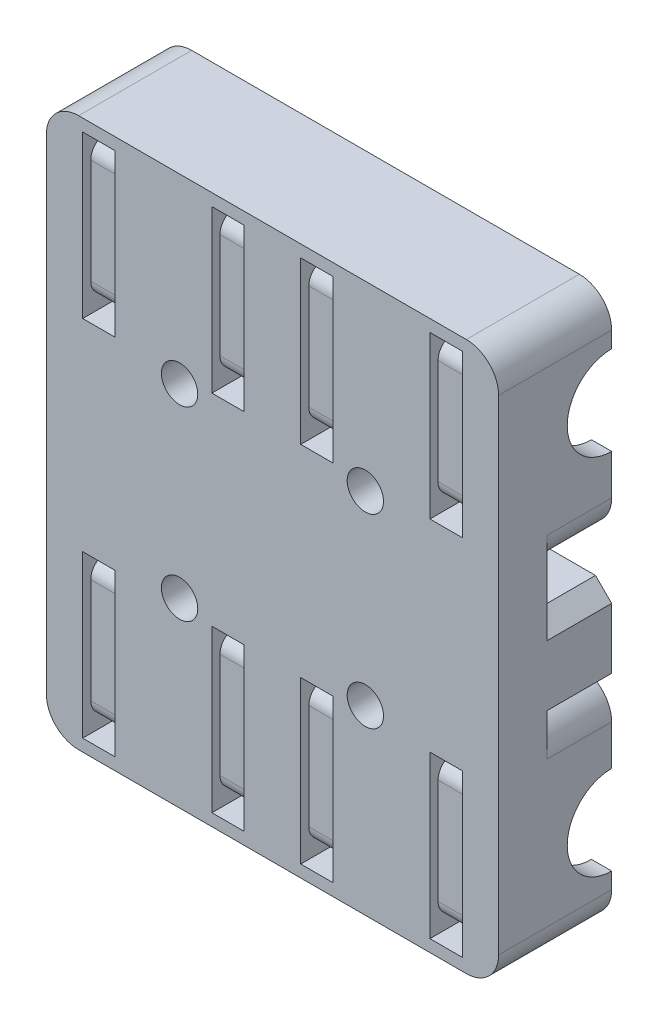
SolidWorks part; units mm, degrees
material "ABS"
ref_plane "Front Plane" through (0, 0, 0) normal (0, 0, 1) x (1, 0, 0)
ref_plane "Top Plane" through (0, 0, 0) normal (0, 1, 0) x (1, 0, 0)
ref_plane "Right Plane" through (0, 0, 0) normal (1, 0, 0) x (0, 0, -1)
sketch "Sketch1" plane through (0, 0, 0) normal (0, 0, 1) x (1, 0, 0)
  line L1 (0, 0) -> (56, 0)
  line L2 (0, 0) -> (0, 68)
  line L3 (0, 68) -> (56, 68)
  line L4 (56, 0) -> (56, 68)
  dimension "D1" = 68
  dimension "D2" = 56
extrude "Boss-Extrude1" add sketch "Sketch1" along normal blind 14
sketch "Sketch2" plane through (0, 0, 14) normal (0, 0, 1) x (1, 0, 0)
  line L0 (0, 34) -> (56, 34) construction
  line L1 (4, 68) -> (52, 68)
  line L2 (0, 64) -> (0, 4)
  line L3 (4, 0) -> (52, 0)
  line L4 (56, 64) -> (56, 4)
  line L5 (4.5, 47.25) -> (0, 47.25) construction
  line L6 (4.5, 48) -> (8.5, 48)
  line L7 (39.5, 45.5) -> (16.5, 45.5) construction
  line L8 (28, 45.5) -> (28, 68) construction
  line L9 (4.5, 48) -> (4.5, 46.5)
  line L10 (4.5, 46.5) -> (8.5, 46.5)
  line L11 (8.5, 48) -> (8.5, 46.5)
  line L12 (0, 68) -> (0, 0) construction
  line L13 (8.5, 47.25) -> (20.5, 47.25) construction
  line L14 (24.5, 47.25) -> (31.5, 47.25) construction
  line L15 (20.5, 48) -> (24.5, 48)
  line L16 (20.5, 48) -> (20.5, 46.5)
  line L17 (20.5, 46.5) -> (24.5, 46.5)
  line L18 (24.5, 48) -> (24.5, 46.5)
  line L19 (35.5, 47.25) -> (47.5, 47.25) construction
  line L20 (31.5, 48) -> (35.5, 48)
  line L21 (31.5, 48) -> (31.5, 46.5)
  line L22 (31.5, 46.5) -> (35.5, 46.5)
  line L23 (35.5, 48) -> (35.5, 46.5)
  line L24 (51.5, 47.25) -> (56, 47.25) construction
  line L25 (47.5, 48) -> (51.5, 48)
  line L26 (47.5, 48) -> (47.5, 46.5)
  line L27 (47.5, 46.5) -> (51.5, 46.5)
  line L28 (51.5, 48) -> (51.5, 46.5)
  line L29 (0, 56.5) -> (56, 56.5) construction
  line L30 (47.5, 65) -> (51.5, 65)
  line L31 (51.5, 65) -> (51.5, 66.5)
  line L32 (47.5, 66.5) -> (51.5, 66.5)
  line L33 (47.5, 65) -> (47.5, 66.5)
  line L34 (35.5, 65) -> (35.5, 66.5)
  line L35 (31.5, 65) -> (35.5, 65)
  line L36 (31.5, 66.5) -> (35.5, 66.5)
  line L37 (31.5, 65) -> (31.5, 66.5)
  line L38 (20.5, 65) -> (24.5, 65)
  line L39 (20.5, 65) -> (20.5, 66.5)
  line L40 (24.5, 65) -> (24.5, 66.5)
  line L41 (20.5, 66.5) -> (24.5, 66.5)
  line L42 (8.5, 65) -> (8.5, 66.5)
  line L43 (4.5, 65) -> (8.5, 65)
  line L44 (4.5, 66.5) -> (8.5, 66.5)
  line L45 (4.5, 65) -> (4.5, 66.5)
  line L46 (8.5, 20) -> (8.5, 21.5)
  line L47 (4.5, 21.5) -> (8.5, 21.5)
  line L48 (4.5, 20) -> (4.5, 21.5)
  line L49 (4.5, 20) -> (8.5, 20)
  line L50 (24.5, 20) -> (24.5, 21.5)
  line L51 (20.5, 21.5) -> (24.5, 21.5)
  line L52 (20.5, 20) -> (20.5, 21.5)
  line L53 (20.5, 20) -> (24.5, 20)
  line L54 (35.5, 20) -> (35.5, 21.5)
  line L55 (31.5, 21.5) -> (35.5, 21.5)
  line L56 (31.5, 20) -> (31.5, 21.5)
  line L57 (31.5, 20) -> (35.5, 20)
  line L58 (51.5, 20) -> (51.5, 21.5)
  line L59 (47.5, 21.5) -> (51.5, 21.5)
  line L60 (47.5, 20) -> (47.5, 21.5)
  line L61 (47.5, 20) -> (51.5, 20)
  line L62 (47.5, 3) -> (47.5, 1.5)
  line L63 (47.5, 1.5) -> (51.5, 1.5)
  line L64 (51.5, 3) -> (51.5, 1.5)
  line L65 (47.5, 3) -> (51.5, 3)
  line L66 (31.5, 3) -> (31.5, 1.5)
  line L67 (31.5, 1.5) -> (35.5, 1.5)
  line L68 (31.5, 3) -> (35.5, 3)
  line L69 (35.5, 3) -> (35.5, 1.5)
  line L70 (20.5, 1.5) -> (24.5, 1.5)
  line L71 (24.5, 3) -> (24.5, 1.5)
  line L72 (20.5, 3) -> (20.5, 1.5)
  line L73 (20.5, 3) -> (24.5, 3)
  line L74 (4.5, 3) -> (4.5, 1.5)
  line L75 (4.5, 1.5) -> (8.5, 1.5)
  line L76 (4.5, 3) -> (8.5, 3)
  line L77 (8.5, 3) -> (8.5, 1.5)
  arc A0 (56, 4) -> (52, 0) centre (52, 4) cw
  arc A1 (4, 0) -> (0, 4) centre (4, 4) cw
  arc A2 (56, 64) -> (52, 68) centre (52, 64) ccw
  arc A3 (4, 68) -> (0, 64) centre (4, 64) ccw
  circle A4 centre (16.5, 22.5) radius 2.25
  circle A5 centre (16.5, 45.5) radius 2.25
  circle A6 centre (39.5, 45.5) radius 2.25
  circle A7 centre (39.5, 22.5) radius 2.25
  point P8 (56, 0)
  point P15 (0, 68)
  line M29 (0, 68) -> (0, 0)
  line M30 (0, 0) -> (56, 0)
  line M31 (56, 0) -> (56, 68)
  line M32 (56, 68) -> (0, 68)
  dimension "D1" = 4
  dimension "D2" = 4.5
  dimension "D3" = 23
  dimension "D4" = 22.5
  dimension "D5" = 1.5
  dimension "D6" = 4
  dimension "D7" = 4.5
  dimension "D8" = 12
  dimension "D9" = 20.75
  dimension "D10" = 9.25
extrude "Cut-Extrude1" cut sketch "Sketch2" against normal through all contours L45 L43 L42 L44 | L41 L39 L38 L40 | L37 L35 L34 L36 | L28 L25 L26 L27 | A6 | L23 L20 L21 L22 | L18 L15 L16 L17 | A5 | L11 L6 L9 L10 | L48 L49 L46 L47 | A4 | L52 L53 L50 L51 | A7 | L73 L72 L70 L71 | A1 M30 M29 | A0 M31 M30 | A3 M32 M29 | A2 M31 M32 | L30 L31 L32 L33 | L57 L54 L55 L56 | L59 L58 L61 L60 | L65 L64 L63 L62 | L67 L69 L68 L66 | L75 L77 L76 L74 region at (0.8935, 67.1065, 14) region at (55.1065, 67.1065, 14) region at (0.8935, 0.8935, 14) region at (55.1065, 0.8935, 14) region at (6.5, 47.25, 14) region at (22.5, 47.25, 14) region at (33.5, 47.25, 14) region at (49.5, 47.25, 14) region at (33.5, 65.75, 14) region at (22.5, 65.75, 14) region at (6.5, 65.75, 14) region at (6.5, 20.75, 14) region at (22.5, 20.75, 14) region at (22.5, 2.25, 14) region at (16.5, 22.5, 14) region at (16.5, 45.5, 14) region at (39.5, 45.5, 14) region at (39.5, 22.5, 14)
sketch "Sketch3" plane through (0, 0, 14) normal (0, 0, 1) x (1, 0, 0)
  line L0 (56, 34) -> (0, 34) construction
  line L1 (4.5, 65) -> (8.5, 65)
  line L2 (4.5, 65) -> (4.5, 48)
  line L3 (4.5, 48) -> (8.5, 48)
  line L4 (8.5, 65) -> (8.5, 48)
  line L5 (20.5, 65) -> (24.5, 65)
  line L6 (20.5, 65) -> (20.5, 48)
  line L7 (20.5, 48) -> (24.5, 48)
  line L8 (24.5, 65) -> (24.5, 48)
  line L9 (31.5, 65) -> (35.5, 65)
  line L10 (31.5, 65) -> (31.5, 48)
  line L11 (31.5, 48) -> (35.5, 48)
  line L12 (35.5, 65) -> (35.5, 48)
  line L13 (47.5, 65) -> (51.5, 65)
  line L14 (47.5, 65) -> (47.5, 48)
  line L15 (47.5, 48) -> (51.5, 48)
  line L16 (51.5, 65) -> (51.5, 48)
  line L17 (56, 4) -> (56, 64) construction
  line L18 (0, 64) -> (0, 4) construction
  line L19 (51.5, 3) -> (51.5, 20)
  line L20 (47.5, 20) -> (51.5, 20)
  line L21 (47.5, 3) -> (47.5, 20)
  line L22 (47.5, 3) -> (51.5, 3)
  line L23 (35.5, 3) -> (35.5, 20)
  line L24 (31.5, 20) -> (35.5, 20)
  line L25 (31.5, 3) -> (31.5, 20)
  line L26 (31.5, 3) -> (35.5, 3)
  line L27 (24.5, 3) -> (24.5, 20)
  line L28 (20.5, 20) -> (24.5, 20)
  line L29 (20.5, 3) -> (20.5, 20)
  line L30 (20.5, 3) -> (24.5, 3)
  line L31 (8.5, 3) -> (8.5, 20)
  line L32 (4.5, 20) -> (8.5, 20)
  line L33 (4.5, 3) -> (4.5, 20)
  line L34 (4.5, 3) -> (8.5, 3)
extrude "Cut-Extrude2" cut sketch "Sketch3" against normal blind 1
ref_plane "Plane2" through (53.5, 0, 0) normal (1, 0, 0) x (0, 0, -1)
sketch "Sketch5" plane through (53.5, 0, 0) normal (1, 0, 0) x (0, 0, -1)
  line L0 (0, 4) -> (0, 64) construction
  line L1 (0, 0) -> (-14, 0) construction
  circle A0 centre (0, 11.5) radius 7.5
  dimension "D1" = 15
  dimension "D2" = 11.5
extrude "Cut-Extrude3" cut sketch "Sketch5" against normal blind 24.5 contours A0
ref_plane "Plane3" through (28, 0, 0) normal (1, 0, 0) x (0, 0, -1)
ref_plane "Plane4" through (0, 34, 0) normal (0, -1, 0) x (-1, 0, 0)
mirror "Mirror1" about plane through (28, 0, 0) normal (1, 0, 0) of "Cut-Extrude3"
sketch "Sketch7" plane through (56, 0, 0) normal (1, 0, 0) x (0, 0, -1)
  line L0 (0, 4) -> (0, 64) construction
  line L1 (0, 0) -> (-14, 0) construction
  circle A0 centre (0, 11.5) radius 5.5
  dimension "D1" = 11
  dimension "D2" = 11.5
extrude "Cut-Extrude4" cut sketch "Sketch7" against normal through all
mirror "Mirror3" about plane through (0, 34, 0) normal (0, -1, 0) of "Cut-Extrude3", "Mirror1", "Cut-Extrude4"
fillet "Fillet1" radius 2 16 edges at (49.5, 3, 13) (33.5, 3, 13) (22.5, 3, 13) (6.5, 3, 13) (6.5, 20, 13) (22.5, 20, 13) (33.5, 20, 13) (49.5, 20, 13) (6.5, 48, 13) (6.5, 65, 13) (22.5, 65, 13) (22.5, 48, 13) (33.5, 48, 13) (33.5, 65, 13) (49.5, 65, 13) (49.5, 48, 13)
sketch "Sketch9" plane through (0, 0, 0) normal (0, 0, -1) x (-1, 0, 0)
  line L0 (-54.91, 27.45) -> (-54.01, 27.45) construction
  line L1 (-52.4311, 27.702) -> (-52.2422, 27.3355)
  line L2 (-53.5978, 27.3355) -> (-53.4089, 27.702)
  line L3 (-54.4211, 27.702) -> (-54.2322, 27.3355)
  line L4 (-54.01, 27.2) -> (-53.82, 27.2)
  line L5 (-55.5878, 27.3355) -> (-55.3989, 27.702)
  line L6 (-54.91, 27.45) -> (-55.81, 27.45) construction
  line L7 (-55.81, 27.2) -> (-56, 27.2)
  line L8 (-50.4411, 27.702) -> (-50.2522, 27.3355)
  line L9 (-29, 19) -> (-53.5, 19) construction
  line L10 (-56, 17) -> (-56, 51) construction
  line L12 (-51.6078, 27.3355) -> (-51.4189, 27.702)
  line L13 (-51.83, 27.2) -> (-52.02, 27.2)
  line L14 (-48.4511, 27.702) -> (-48.2622, 27.3355)
  line L15 (-49.6178, 27.3355) -> (-49.4289, 27.702)
  line L16 (-49.84, 27.2) -> (-50.03, 27.2)
  line L17 (-46.4611, 27.702) -> (-46.2722, 27.3355)
  line L18 (-47.6278, 27.3355) -> (-47.4389, 27.702)
  line L19 (-47.85, 27.2) -> (-48.04, 27.2)
  line L20 (-44.4711, 27.702) -> (-44.2822, 27.3355)
  line L21 (-45.6378, 27.3355) -> (-45.4489, 27.702)
  line L22 (-45.86, 27.2) -> (-46.05, 27.2)
  line L23 (-42.4811, 27.702) -> (-42.2922, 27.3355)
  line L24 (-43.6478, 27.3355) -> (-43.4589, 27.702)
  line L25 (-43.87, 27.2) -> (-44.06, 27.2)
  line L26 (-40.4911, 27.702) -> (-40.3022, 27.3355)
  line L27 (-41.6578, 27.3355) -> (-41.4689, 27.702)
  line L28 (-41.88, 27.2) -> (-42.07, 27.2)
  line L29 (-38.5011, 27.702) -> (-38.3122, 27.3355)
  line L30 (-39.6678, 27.3355) -> (-39.4789, 27.702)
  line L31 (-39.89, 27.2) -> (-40.08, 27.2)
  line L32 (-36.5111, 27.702) -> (-36.3222, 27.3355)
  line L33 (-37.6778, 27.3355) -> (-37.4889, 27.702)
  line L34 (-37.9, 27.2) -> (-38.09, 27.2)
  line L35 (-34.5211, 27.702) -> (-34.3322, 27.3355)
  line L36 (-35.6878, 27.3355) -> (-35.4989, 27.702)
  line L37 (-35.91, 27.2) -> (-36.1, 27.2)
  line L38 (-34.11, 27.2) -> (-34.11, 34.7)
  line L39 (-36.11, 36.7) -> (-54, 36.7)
  line L40 (-56, 34.7) -> (-56, 27.2)
  line L41 (-54, 36.7) -> (-56, 34.7)
  line L42 (-34.11, 34.7) -> (-36.11, 36.7)
  line L43 (-52, 26) -> (-4, 26)
  line L44 (-1.09, 27.45) -> (-0.19, 27.45) construction
  line L45 (-52, 42) -> (-4, 42)
  line L46 (-1.09, 27.45) -> (-1.99, 27.45) construction
  line L47 (-48.94, 28) -> (-48.94, 26) construction
  line L48 (-56, 46) -> (-56, 22)
  line L49 (-28, 42) -> (-28, 26) construction
  line L50 (0, 46) -> (0, 22)
  line L51 (-21.89, 34.7) -> (-19.89, 36.7)
  line L52 (-2, 36.7) -> (0, 34.7)
  line L53 (0, 34.7) -> (0, 27.2)
  line L54 (-19.89, 36.7) -> (-2, 36.7)
  line L55 (-21.89, 27.2) -> (-21.89, 34.7)
  line L56 (-20.09, 27.2) -> (-19.9, 27.2)
  line L57 (-20.3122, 27.3355) -> (-20.5011, 27.702)
  line L58 (-21.4789, 27.702) -> (-21.6678, 27.3355)
  line L59 (-18.1, 27.2) -> (-17.91, 27.2)
  line L60 (-18.3222, 27.3355) -> (-18.5111, 27.702)
  line L61 (-19.4889, 27.702) -> (-19.6778, 27.3355)
  line L62 (-16.11, 27.2) -> (-15.92, 27.2)
  line L63 (-16.3322, 27.3355) -> (-16.5211, 27.702)
  line L64 (-17.4989, 27.702) -> (-17.6878, 27.3355)
  line L65 (-14.12, 27.2) -> (-13.93, 27.2)
  line L66 (-14.3422, 27.3355) -> (-14.5311, 27.702)
  line L67 (-15.5089, 27.702) -> (-15.6978, 27.3355)
  line L68 (-12.13, 27.2) -> (-11.94, 27.2)
  line L69 (-12.3522, 27.3355) -> (-12.5411, 27.702)
  line L70 (-13.5189, 27.702) -> (-13.7078, 27.3355)
  line L71 (-10.14, 27.2) -> (-9.95, 27.2)
  line L72 (-10.3622, 27.3355) -> (-10.5511, 27.702)
  line L73 (-11.5289, 27.702) -> (-11.7178, 27.3355)
  line L74 (-8.15, 27.2) -> (-7.96, 27.2)
  line L75 (-8.3722, 27.3355) -> (-8.5611, 27.702)
  line L76 (-9.5389, 27.702) -> (-9.7278, 27.3355)
  line L77 (-6.16, 27.2) -> (-5.97, 27.2)
  line L78 (-6.3822, 27.3355) -> (-6.5711, 27.702)
  line L79 (-7.5489, 27.702) -> (-7.7378, 27.3355)
  line L80 (-4.17, 27.2) -> (-3.98, 27.2)
  line L81 (-4.3922, 27.3355) -> (-4.5811, 27.702)
  line L82 (-5.5589, 27.702) -> (-5.7478, 27.3355)
  line L83 (-0.19, 27.2) -> (0, 27.2)
  line L84 (-0.4122, 27.3355) -> (-0.6011, 27.702)
  line L85 (-1.99, 27.2) -> (-2.18, 27.2)
  line L86 (-1.5789, 27.702) -> (-1.7678, 27.3355)
  line L87 (-2.4022, 27.3355) -> (-2.5911, 27.702)
  line L88 (-3.5689, 27.702) -> (-3.7578, 27.3355)
  arc A0 (-54.4211, 27.702) -> (-55.3989, 27.702) centre (-54.91, 27.45) ccw
  arc A1 (-54.2322, 27.3355) -> (-54.01, 27.2) centre (-54.01, 27.45) ccw
  arc A2 (-55.81, 27.2) -> (-55.5878, 27.3355) centre (-55.81, 27.45) ccw
  arc A3 (-52.2422, 27.3355) -> (-52.02, 27.2) centre (-52.02, 27.45) ccw
  arc A4 (-52.4311, 27.702) -> (-53.4089, 27.702) centre (-52.92, 27.45) ccw
  arc A5 (-53.82, 27.2) -> (-53.5978, 27.3355) centre (-53.82, 27.45) ccw
  arc A6 (-50.2522, 27.3355) -> (-50.03, 27.2) centre (-50.03, 27.45) ccw
  arc A7 (-50.4411, 27.702) -> (-51.4189, 27.702) centre (-50.93, 27.45) ccw
  arc A8 (-51.83, 27.2) -> (-51.6078, 27.3355) centre (-51.83, 27.45) ccw
  arc A9 (-48.2622, 27.3355) -> (-48.04, 27.2) centre (-48.04, 27.45) ccw
  arc A10 (-48.4511, 27.702) -> (-49.4289, 27.702) centre (-48.94, 27.45) ccw
  arc A11 (-49.84, 27.2) -> (-49.6178, 27.3355) centre (-49.84, 27.45) ccw
  arc A12 (-46.2722, 27.3355) -> (-46.05, 27.2) centre (-46.05, 27.45) ccw
  arc A13 (-46.4611, 27.702) -> (-47.4389, 27.702) centre (-46.95, 27.45) ccw
  arc A14 (-47.85, 27.2) -> (-47.6278, 27.3355) centre (-47.85, 27.45) ccw
  arc A15 (-44.2822, 27.3355) -> (-44.06, 27.2) centre (-44.06, 27.45) ccw
  arc A16 (-44.4711, 27.702) -> (-45.4489, 27.702) centre (-44.96, 27.45) ccw
  arc A17 (-45.86, 27.2) -> (-45.6378, 27.3355) centre (-45.86, 27.45) ccw
  arc A18 (-42.2922, 27.3355) -> (-42.07, 27.2) centre (-42.07, 27.45) ccw
  arc A19 (-42.4811, 27.702) -> (-43.4589, 27.702) centre (-42.97, 27.45) ccw
  arc A20 (-43.87, 27.2) -> (-43.6478, 27.3355) centre (-43.87, 27.45) ccw
  arc A21 (-40.3022, 27.3355) -> (-40.08, 27.2) centre (-40.08, 27.45) ccw
  arc A22 (-40.4911, 27.702) -> (-41.4689, 27.702) centre (-40.98, 27.45) ccw
  arc A23 (-41.88, 27.2) -> (-41.6578, 27.3355) centre (-41.88, 27.45) ccw
  arc A24 (-38.3122, 27.3355) -> (-38.09, 27.2) centre (-38.09, 27.45) ccw
  arc A25 (-38.5011, 27.702) -> (-39.4789, 27.702) centre (-38.99, 27.45) ccw
  arc A26 (-39.89, 27.2) -> (-39.6678, 27.3355) centre (-39.89, 27.45) ccw
  arc A27 (-36.3222, 27.3355) -> (-36.1, 27.2) centre (-36.1, 27.45) ccw
  arc A28 (-36.5111, 27.702) -> (-37.4889, 27.702) centre (-37, 27.45) ccw
  arc A29 (-37.9, 27.2) -> (-37.6778, 27.3355) centre (-37.9, 27.45) ccw
  arc A30 (-34.3322, 27.3355) -> (-34.11, 27.2) centre (-34.11, 27.45) ccw
  arc A31 (-34.5211, 27.702) -> (-35.4989, 27.702) centre (-35.01, 27.45) ccw
  arc A32 (-35.91, 27.2) -> (-35.6878, 27.3355) centre (-35.91, 27.45) ccw
  arc A33 (-52, 26) -> (-56, 22) centre (-52, 22) ccw
  arc A34 (-56, 46) -> (-52, 42) centre (-52, 46) ccw
  arc A35 (0, 46) -> (-4, 42) centre (-4, 46) cw
  arc A36 (-4, 26) -> (0, 22) centre (-4, 22) cw
  arc A37 (-20.09, 27.2) -> (-20.3122, 27.3355) centre (-20.09, 27.45) cw
  arc A38 (-21.4789, 27.702) -> (-20.5011, 27.702) centre (-20.99, 27.45) cw
  arc A39 (-21.6678, 27.3355) -> (-21.89, 27.2) centre (-21.89, 27.45) cw
  arc A40 (-18.1, 27.2) -> (-18.3222, 27.3355) centre (-18.1, 27.45) cw
  arc A41 (-19.4889, 27.702) -> (-18.5111, 27.702) centre (-19, 27.45) cw
  arc A42 (-19.6778, 27.3355) -> (-19.9, 27.2) centre (-19.9, 27.45) cw
  arc A43 (-16.11, 27.2) -> (-16.3322, 27.3355) centre (-16.11, 27.45) cw
  arc A44 (-17.4989, 27.702) -> (-16.5211, 27.702) centre (-17.01, 27.45) cw
  arc A45 (-17.6878, 27.3355) -> (-17.91, 27.2) centre (-17.91, 27.45) cw
  arc A46 (-14.12, 27.2) -> (-14.3422, 27.3355) centre (-14.12, 27.45) cw
  arc A47 (-15.5089, 27.702) -> (-14.5311, 27.702) centre (-15.02, 27.45) cw
  arc A48 (-15.6978, 27.3355) -> (-15.92, 27.2) centre (-15.92, 27.45) cw
  arc A49 (-12.13, 27.2) -> (-12.3522, 27.3355) centre (-12.13, 27.45) cw
  arc A50 (-13.5189, 27.702) -> (-12.5411, 27.702) centre (-13.03, 27.45) cw
  arc A51 (-13.7078, 27.3355) -> (-13.93, 27.2) centre (-13.93, 27.45) cw
  arc A52 (-10.14, 27.2) -> (-10.3622, 27.3355) centre (-10.14, 27.45) cw
  arc A53 (-11.5289, 27.702) -> (-10.5511, 27.702) centre (-11.04, 27.45) cw
  arc A54 (-11.7178, 27.3355) -> (-11.94, 27.2) centre (-11.94, 27.45) cw
  arc A55 (-8.15, 27.2) -> (-8.3722, 27.3355) centre (-8.15, 27.45) cw
  arc A56 (-9.5389, 27.702) -> (-8.5611, 27.702) centre (-9.05, 27.45) cw
  arc A57 (-9.7278, 27.3355) -> (-9.95, 27.2) centre (-9.95, 27.45) cw
  arc A58 (-6.16, 27.2) -> (-6.3822, 27.3355) centre (-6.16, 27.45) cw
  arc A59 (-7.5489, 27.702) -> (-6.5711, 27.702) centre (-7.06, 27.45) cw
  arc A60 (-7.7378, 27.3355) -> (-7.96, 27.2) centre (-7.96, 27.45) cw
  arc A61 (-4.17, 27.2) -> (-4.3922, 27.3355) centre (-4.17, 27.45) cw
  arc A62 (-5.5589, 27.702) -> (-4.5811, 27.702) centre (-5.07, 27.45) cw
  arc A63 (-5.7478, 27.3355) -> (-5.97, 27.2) centre (-5.97, 27.45) cw
  arc A64 (-2.18, 27.2) -> (-2.4022, 27.3355) centre (-2.18, 27.45) cw
  arc A65 (-3.5689, 27.702) -> (-2.5911, 27.702) centre (-3.08, 27.45) cw
  arc A66 (-3.7578, 27.3355) -> (-3.98, 27.2) centre (-3.98, 27.45) cw
  arc A67 (-0.19, 27.2) -> (-0.4122, 27.3355) centre (-0.19, 27.45) cw
  arc A68 (-1.7678, 27.3355) -> (-1.99, 27.2) centre (-1.99, 27.45) cw
  arc A69 (-1.5789, 27.702) -> (-0.6011, 27.702) centre (-1.09, 27.45) cw
  point P5 (-56, 36.7)
  point P120 (-34.11, 36.7)
  point P127 (-41.25, 19)
  dimension "D1" = 1.1
  dimension "D2" = 0.5
  dimension "D5" = 0.19
  dimension "D13" = 8
  dimension "D4" = 0.19
  dimension "D7" = 2
  dimension "D8" = 9.5
  dimension "D9" = 2
  dimension "D10" = 45
  dimension "D11" = 2
  dimension "D12" = 45
  dimension "D14" = 24
  dimension "D15" = 16
  dimension "D16" = 7
extrude "Cut-Extrude6" cut sketch "Sketch9" against normal blind 8 contours A69 L86 A68 L85 A64 L87 A65 L88 A66 L80 A61 L81 A62 L82 A63 L77 A58 L78 A59 L79 A60 L74 A55 L75 A56 L76 A57 L71 A52 L72 A53 L73 A54 L68 A49 L69 A50 L70 A51 L65 A46 L66 A47 L67 A48 L62 A43 L63 A44 L64 A45 region at (28, 35.4413, 0)
